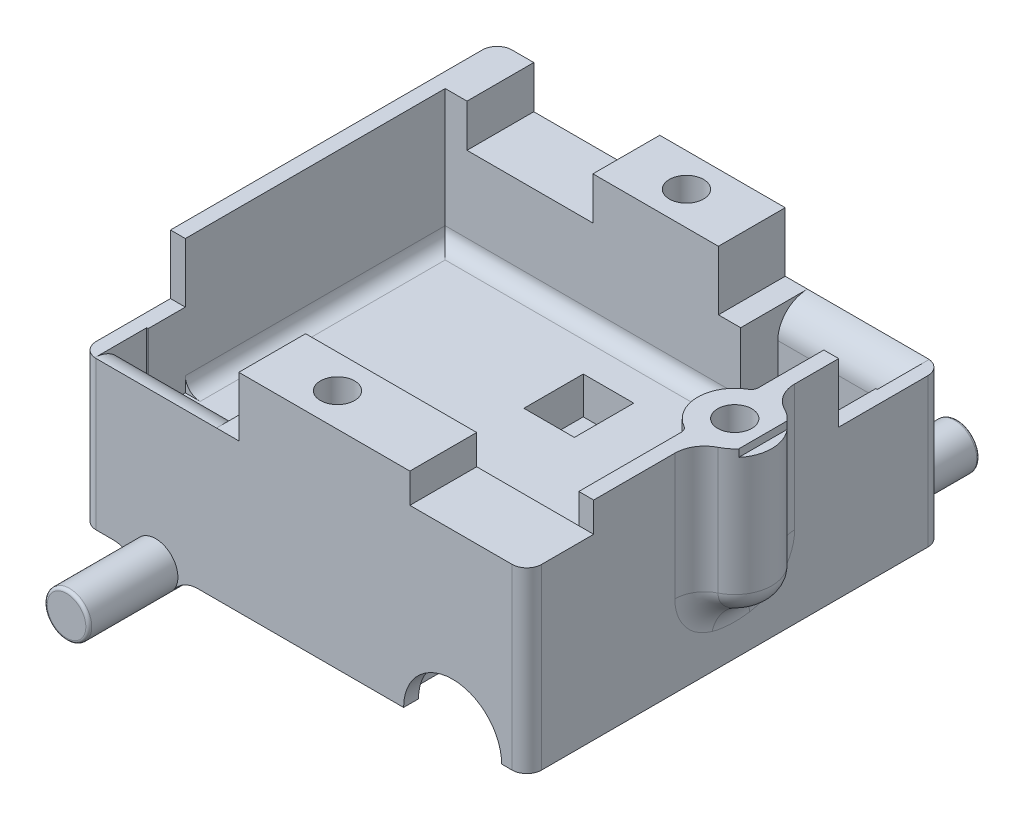
SolidWorks part; units mm, degrees
ref_plane "Front Plane" through (0, 0, 0) normal (0, 0, 1) x (1, 0, 0)
ref_plane "Top Plane" through (0, 0, 0) normal (0, 1, 0) x (1, 0, 0)
ref_plane "Right Plane" through (0, 0, 0) normal (1, 0, 0) x (0, 0, -1)
sketch "Sketch4" plane through (0, 0, 0) normal (0, 1, 0) x (1, 0, 0)
  line L1 (-14.8464, 7.0648) -> (15.1536, 7.0648)
  line L2 (-14.8464, 7.0648) -> (-14.8464, -20.9352)
  line L3 (-14.8464, -20.9352) -> (15.1536, -20.9352)
  line L4 (15.1536, 7.0648) -> (15.1536, -20.9352)
  dimension "D1" = 30
  dimension "D2" = 28
extrude "Boss-Extrude2" add sketch "Sketch4" along normal blind 14
sketch "Sketch20" plane through (0, 14, 0) normal (0, 1, 0) x (1, 0, 0)
  line L0 (-14.8464, -20.9352) -> (15.1536, -20.9352) construction
  line L1 (14.1536, -16.4352) -> (-13.8464, -16.4352)
  line L2 (14.1536, -16.4352) -> (14.1536, 2.5648)
  line L3 (14.1536, 2.5648) -> (-13.8464, 2.5648)
  line L4 (-13.8464, -16.4352) -> (-13.8464, 2.5648)
  line L5 (15.1536, -20.9352) -> (15.1536, 7.0648) construction
  dimension "D1" = 19
  dimension "D2" = 4.5
  dimension "D3" = 28
  dimension "D4" = 1
extrude "Cut-Extrude16" cut sketch "Sketch20" against normal blind 9
fillet "Fillet10" radius 1 4 edges at (0.1536, 5, 16.4352) (-13.8464, 5, 6.9352) (0.1536, 5, -2.5648) (14.1536, 5, 6.9352)
sketch "Sketch26" plane through (0, 0, 20.9352) normal (0, 0, 1) x (1, 0, 0)
  circle A0 centre (10.1536, 0) radius 4.1
  dimension "D1" = 8.2
extrude "Cut-Extrude17" cut sketch "Sketch26" against normal blind 26
sketch "Sketch27" plane through (0, 0, -7.0648) normal (0, 0, -1) x (-1, 0, 0)
  circle A0 centre (9.8464, 0) radius 4.1
  dimension "D1" = 8.2
extrude "Cut-Extrude18" cut sketch "Sketch27" against normal blind 26
sketch "Sketch28" plane through (0, 0, 0) normal (0, -1, 0) x (1, 0, 0)
  line L0 (-5.7464, 18.9352) -> (-5.7464, -7.0648) construction
  line L1 (-13.9464, -7.0648) -> (-5.7464, -7.0648)
  line L2 (-13.9464, -7.0648) -> (-13.9464, -6.0648)
  line L3 (-13.9464, -6.0648) -> (-5.7464, -6.0648)
  line L4 (-5.7464, -7.0648) -> (-5.7464, -6.0648)
  line L5 (14.2536, 20.9352) -> (14.2536, -5.0648) construction
  line L6 (6.0536, 20.9352) -> (14.2536, 20.9352)
  line L7 (6.0536, 20.9352) -> (6.0536, 19.9352)
  line L8 (6.0536, 19.9352) -> (14.2536, 19.9352)
  line L9 (14.2536, 20.9352) -> (14.2536, 19.9352)
  dimension "D1" = 1
  dimension "D2" = 1
extrude "Boss-Extrude6" add sketch "Sketch28" against normal blind 9
sketch "Sketch29" plane through (0, 0, -7.0648) normal (0, 0, -1) x (-1, 0, 0)
  circle A0 centre (9.8464, 0) radius 3.3
  dimension "D1" = 6.6
extrude "Cut-Extrude19" cut sketch "Sketch29" against normal blind 1
sketch "Sketch30" plane through (0, 0, 20.9352) normal (0, 0, 1) x (1, 0, 0)
  circle A0 centre (10.1536, 0) radius 3.3
  dimension "D1" = 6.6
extrude "Cut-Extrude20" cut sketch "Sketch30" against normal blind 1
sketch "Sketch31" plane through (0, 0, 18.9352) normal (0, 0, -1) x (-1, 0, 0)
  line L0 (5.7464, 0) -> (13.9464, 0) construction
  circle A0 centre (9.8464, 0) radius 1.5
  dimension "D1" = 3
extrude "Boss-Extrude7" add sketch "Sketch31" against normal blind 8
sketch "Sketch32" plane through (0, 0, -5.0648) normal (0, 0, 1) x (1, 0, 0)
  line L0 (6.0536, 0) -> (14.2536, 0) construction
  circle A0 centre (10.1536, 0) radius 1.5
  dimension "D1" = 3
extrude "Boss-Extrude8" add sketch "Sketch32" against normal blind 8
fillet "Fillet12" radius 2 4 edges at (-8.3464, 0, 19.9352) (-11.3464, 0, 19.9352) (8.6536, 0, -6.0648) (11.6536, 0, -6.0648)
sketch "Sketch33" plane through (0, 0, 0) normal (0, -1, 0) x (1, 0, 0)
  line L0 (14.2536, 19.9352) -> (14.2536, -5.0648) construction
  line L1 (6.0536, -5.0648) -> (14.2536, -5.0648)
  line L2 (6.0536, -5.0648) -> (6.0536, -3.5648)
  line L3 (6.0536, -3.5648) -> (14.2536, -3.5648)
  line L4 (14.2536, -5.0648) -> (14.2536, -3.5648)
  line L5 (-13.9464, -6.0648) -> (-13.9464, 18.9352) construction
  line L6 (-5.7464, 18.9352) -> (-13.9464, 18.9352)
  line L7 (-5.7464, 18.9352) -> (-5.7464, 17.4352)
  line L8 (-5.7464, 17.4352) -> (-13.9464, 17.4352)
  line L9 (-13.9464, 18.9352) -> (-13.9464, 17.4352)
  dimension "D1" = 1.5
  dimension "D2" = 1.5
extrude "Cut-Extrude21" cut sketch "Sketch33" against normal through all
fillet "Fillet13" radius 0.2 2 edges at (11.6536, 0, -13.0648) (-11.3464, 0, 26.9352)
fillet "Fillet15" radius 1 4 edges at (15.1536, 7, 20.9352) (15.1536, 7, -7.0648) (-14.8464, 7, -7.0648) (-14.8464, 7, 20.9352)
sketch "Sketch34" plane through (0, 14, 0) normal (0, 1, 0) x (1, 0, 0)
  line L0 (15.1536, -19.9352) -> (15.1536, 6.0648) construction
  circle A0 centre (15.1536, -6.9352) radius 2.5
  dimension "D1" = 5
extrude "Boss-Extrude9" add sketch "Sketch34" against normal blind 10
fillet "Fillet16" radius 1.5 1 edges at (17.6536, 4, 6.9352)
fillet "Fillet17" radius 2 5 edges at (15.1536, 9.75, 9.4352) (15.1536, 9.75, 4.4352) (15.1536, 4.4393, 8.9958) (15.1536, 4.4393, 4.8745) (15.1536, 4, 6.9352)
fillet "Fillet18" radius 0.5 5 edges at (13.9723, 5.4258, 9.1384) (13.8531, 5.2853, 4.8001) (14.1536, 10, 9.2264) (14.1536, 10, 4.6439) (12.6536, 5, 6.9352)
sketch "Sketch35" plane through (0, 14, 0) normal (0, 1, 0) x (1, 0, 0)
  circle A0 centre (15.1536, -6.9352) radius 1.15
  dimension "D1" = 2.3
extrude "Cut-Extrude22" cut sketch "Sketch35" against normal blind 8
sketch "Sketch36" plane through (0, 14, 0) normal (0, 1, 0) x (1, 0, 0)
  line L0 (14.1536, 2.5648) -> (-13.8464, 2.5648) construction
  line L1 (-14.8464, 6.0648) -> (-14.8464, -19.9352) construction
  line L2 (-13.8464, -20.9352) -> (14.1536, -20.9352) construction
  circle A0 centre (0.1536, -18.6852) radius 1.15
  circle A1 centre (0.1536, 4.8148) radius 1.15
  dimension "D1" = 2.3
  dimension "D2" = 2.3
  dimension "D3" = 2.25
  dimension "D4" = 15
  dimension "D5" = 2.25
  dimension "D6" = 15
extrude "Cut-Extrude23" cut sketch "Sketch36" against normal through all
sketch "Sketch37" plane through (0, 0, -5.0648) normal (0, 0, 1) x (1, 0, 0)
  line L0 (14.2536, 14) -> (14.2536, 0) construction
  line L1 (6.0536, 14) -> (14.2536, 14)
  line L2 (6.0536, 14) -> (6.0536, 10)
  line L3 (6.0536, 10) -> (14.2536, 10)
  line L4 (14.2536, 14) -> (14.2536, 10)
  dimension "D1" = 4
extrude "Cut-Extrude24" cut sketch "Sketch37" against normal blind 2
fillet "Fillet19" radius 2 1 edges at (10.1536, 10, -5.0648)
sketch "Sketch38" plane through (0, 0, 18.9352) normal (0, 0, -1) x (-1, 0, 0)
  line L0 (13.9464, 14) -> (13.9464, 0) construction
  line L1 (5.7464, 14) -> (13.9464, 14)
  line L2 (5.7464, 14) -> (5.7464, 10)
  line L3 (5.7464, 10) -> (13.9464, 10)
  line L4 (13.9464, 14) -> (13.9464, 10)
  dimension "D1" = 4
extrude "Cut-Extrude25" cut sketch "Sketch38" against normal blind 2
fillet "Fillet20" radius 2 1 edges at (-9.8464, 10, 18.9352)
sketch "Sketch39" plane through (0, 0, 0) normal (0, -1, 0) x (1, 0, 0)
  line L0 (15.1536, 19.9352) -> (15.1536, -6.0648) construction
  line L1 (7.2813, -7.0648) -> (-6.5464, -7.0648) construction
  line L2 (-6.9741, 20.9352) -> (6.8536, 20.9352) construction
  circle A0 centre (0.1536, 2.4352) radius 0.9
  circle A2 centre (0.1536, 11.4352) radius 0.9
  dimension "D1" = 15
  dimension "D2" = 15
  dimension "D3" = 9.5
  dimension "D4" = 9.5
  dimension "D5" = 1.8
  dimension "D6" = 1.8
extrude "Cut-Extrude26" cut sketch "Sketch39" against normal through all and the other way through all
sketch "Sketch40" plane through (0, 5, 0) normal (0, 1, 0) x (1, 0, 0)
  line L1 (-1.5464, -0.4352) -> (1.8536, -0.4352)
  line L2 (-1.5464, -0.4352) -> (-1.5464, -4.4352)
  line L3 (-1.5464, -4.4352) -> (1.8536, -4.4352)
  line L4 (1.8536, -0.4352) -> (1.8536, -4.4352)
  line L5 (-1.5464, -9.4352) -> (1.8536, -9.4352)
  line L6 (-1.5464, -9.4352) -> (-1.5464, -13.4352)
  line L7 (-1.5464, -13.4352) -> (1.8536, -13.4352)
  line L8 (1.8536, -9.4352) -> (1.8536, -13.4352)
  circle A0 centre (0.1536, -2.4352) radius 0.9 construction
  circle A1 centre (0.1536, -11.4352) radius 0.9 construction
  dimension "D1" = 3.4
  dimension "D2" = 3.4
  dimension "D3" = 4
  dimension "D4" = 4
  dimension "D5" = 2
  dimension "D6" = 1.7
  dimension "D7" = 1.7
  dimension "D8" = 2
extrude "Cut-Extrude27" cut sketch "Sketch40" against normal blind 2.5
sketch "Sketch41" plane through (0, 0, -7.0648) normal (0, 0, -1) x (-1, 0, 0)
  line L0 (-6.0536, 14) -> (13.8464, 14) construction
  line L1 (3.8964, 14) -> (12.3775, 14)
  line L2 (3.8964, 14) -> (3.8964, 11.1303)
  line L3 (3.8964, 11.1303) -> (12.3775, 11.1303)
  line L4 (12.3775, 14) -> (12.3775, 11.1303)
extrude "Cut-Extrude28" cut sketch "Sketch41" against normal blind 10
sketch "Sketch42" plane through (0, 0, -7.0648) normal (0, 0, -1) x (-1, 0, 0)
  line L1 (-6.0536, 10) -> (-16.2647, 10)
  line L2 (-6.0536, 10) -> (-6.0536, 14)
  line L3 (-6.0536, 14) -> (-16.2647, 14)
  line L4 (-16.2647, 10) -> (-16.2647, 14)
extrude "Cut-Extrude29" cut sketch "Sketch42" against normal blind 7
sketch "Sketch43" plane through (0, 14, 0) normal (0, 1, 0) x (1, 0, 0)
  line L0 (15.1536, -19.9352) -> (15.1536, -10.9663) construction
  line L1 (15.1536, -16.4352) -> (7.2753, -16.4352)
  line L2 (15.1536, -16.4352) -> (15.1536, -20.9352)
  line L3 (15.1536, -20.9352) -> (7.2753, -20.9352)
  line L4 (7.2753, -16.4352) -> (7.2753, -20.9352)
  line L5 (-5.7464, -20.9352) -> (14.1536, -20.9352) construction
extrude "Cut-Extrude30" cut sketch "Sketch43" against normal blind 2
sketch "Sketch44" plane through (0, 14, 0) normal (0, 1, 0) x (1, 0, 0)
  line L1 (17.052, -8.7906) -> (17.8177, -8.7906)
  line L2 (17.052, -8.7906) -> (17.052, -5.0159)
  line L3 (17.052, -5.0159) -> (17.8177, -5.0159)
  line L4 (17.8177, -8.7906) -> (17.8177, -5.0159)
extrude "Cut-Extrude31" cut sketch "Sketch44" against normal blind 0.5
sketch "Sketch45" plane through (0, 0, 20.9352) normal (0, 0, 1) x (1, 0, 0)
  line L1 (-5.7464, 10) -> (-15.5344, 10)
  line L2 (-5.7464, 10) -> (-5.7464, 14)
  line L3 (-5.7464, 14) -> (-15.5344, 14)
  line L4 (-15.5344, 10) -> (-15.5344, 14)
extrude "Cut-Extrude32" cut sketch "Sketch45" against normal up to surface (3.5 mm away) up to face at (-9.8464, 8.025, 17.4352)
sketch "Sketch46" plane through (0, 0, 20.9352) normal (0, 0, 1) x (1, 0, 0)
  line L0 (-5.7464, 14) -> (7.2753, 14) construction
  line L1 (-5.7464, 10) -> (-4.2464, 10)
  line L2 (-5.7464, 10) -> (-5.7464, 14)
  line L3 (-5.7464, 14) -> (-4.2464, 14)
  line L4 (-4.2464, 10) -> (-4.2464, 14)
  dimension "D1" = 1.5
extrude "Cut-Extrude33" cut sketch "Sketch46" against normal up to surface (3.5 mm away) up to face at (-11.5131, 8.6833, 17.4352)
sketch "Sketch47" plane through (0, 0, 17.4352) normal (0, 0, 1) x (1, 0, 0)
  line L1 (-14.8464, 10) -> (-4.2464, 10)
  line L2 (-14.8464, 10) -> (-14.8464, 14)
  line L3 (-14.8464, 14) -> (-4.2464, 14)
  line L4 (-4.2464, 10) -> (-4.2464, 14)
extrude "Cut-Extrude34" cut sketch "Sketch47" against normal blind 2.5
sketch "Sketch48" plane through (0, 0, -7.0648) normal (0, 0, -1) x (-1, 0, 0)
  line L0 (-6.0536, 14) -> (3.8964, 14) construction
  line L1 (-6.0536, 10) -> (-4.5536, 10)
  line L2 (-6.0536, 10) -> (-6.0536, 14)
  line L3 (-6.0536, 14) -> (-4.5536, 14)
  line L4 (-4.5536, 10) -> (-4.5536, 14)
  dimension "D1" = 1.5
extrude "Cut-Extrude35" cut sketch "Sketch48" against normal blind 4.5
sketch "Sketch49" plane through (0, 0, 0) normal (0, -1, 0) x (1, 0, 0)
  circle A0 centre (-3.5474, -1.7648) radius 2
  circle A1 centre (-3.5474, 15.6352) radius 2
  circle A2 centre (3.8526, 15.6352) radius 2
  dimension "D1" = 4
  dimension "D2" = 4
  dimension "D3" = 4
extrude "Cut-Extrude36" cut sketch "Sketch49" against normal blind 1.5
sketch "Sketch50" plane through (0, 0, 0) normal (0, -1, 0) x (1, 0, 0)
  line L0 (-5.1274, -3.3648) -> (-5.1274, 17.2352) construction
  line L1 (-5.1274, 14.9352) -> (5.4346, 14.9352)
  line L2 (-5.1274, 14.9352) -> (-5.1274, -1.0648)
  line L3 (-5.1274, -1.0648) -> (5.4346, -1.0648)
  line L4 (5.4346, 14.9352) -> (5.4346, -1.0648)
  line L5 (5.4346, 17.2352) -> (5.4346, 6.4629) construction
  line L6 (7.2813, -7.0648) -> (-6.5464, -7.0648) construction
  line L7 (-6.9741, 20.9352) -> (6.8536, 20.9352) construction
  dimension "D1" = 6
  dimension "D2" = 6
extrude "Cut-Extrude37" cut sketch "Sketch50" against normal blind 1.5
sketch "Sketch51" plane through (0, 10, 0) normal (0, 1, 0) x (1, 0, 0)
  line L1 (-5.7464, -17.4352) -> (-13.8464, -17.4352)
  line L2 (-5.7464, -17.4352) -> (-5.7464, -14.9352)
  line L3 (-5.7464, -14.9352) -> (-13.8464, -14.9352)
  line L4 (-13.8464, -17.4352) -> (-13.8464, -14.9352)
  line L5 (6.0536, 3.5648) -> (14.1536, 3.5648)
  line L6 (6.0536, 3.5648) -> (6.0536, 0.0648)
  line L7 (6.0536, 0.0648) -> (14.1536, 0.0648)
  line L8 (14.1536, 3.5648) -> (14.1536, 0.0648)
extrude "Cut-Extrude38" cut sketch "Sketch51" against normal up to surface (5 mm away) up to face at (0.1536, 5, 2.4352)
sketch "Sketch52" plane through (0, 0, 18.9352) normal (0, 0, -1) x (-1, 0, 0)
  circle A0 centre (9.8464, 0) radius 1.5
extrude "Boss-Extrude10" add sketch "Sketch52" along normal blind 0.5
sketch "Sketch53" plane through (0, 0, -5.0648) normal (0, 0, 1) x (1, 0, 0)
  circle A0 centre (10.1536, 0) radius 1.5
extrude "Boss-Extrude11" add sketch "Sketch53" along normal blind 0.5
